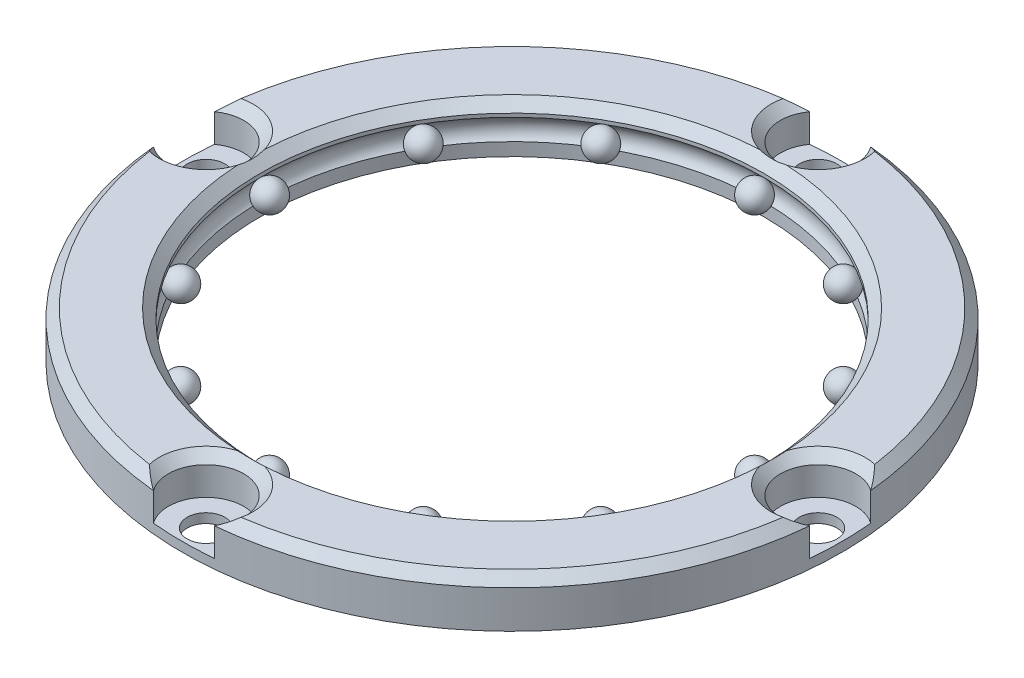
SolidWorks part; units mm, degrees
ref_plane "Front Plane" through (0, 0, 0) normal (0, 0, 1) x (1, 0, 0)
ref_plane "Top Plane" through (0, 0, 0) normal (0, 1, 0) x (1, 0, 0)
ref_plane "Right Plane" through (0, 0, 0) normal (1, 0, 0) x (0, 0, -1)
sketch "Sketch1" plane through (0, 0, 0) normal (0, 1, 0) x (1, 0, 0)
  line L0 (0, 0) -> (0, 19) construction
  circle A1 centre (0, 19) radius 8.5 construction
  circle A2 centre (19, 0) radius 3
  circle A3 centre (19, 0) radius 1.5313
  circle A5 centre (0, 19) radius 10 construction
  circle A10 centre (0, 19) radius 3
  circle A12 centre (0, -19) radius 3
  circle A14 centre (0, 19) radius 1.5313
  circle A17 centre (0, -19) radius 1.5313
  circle A18 centre (-19, 0) radius 3
  circle A19 centre (-19, 0) radius 1.5313
  point P13 (0, 0)
  point P24 (0, 0)
  point P26 (0, 0)
  point P30 (0, 0)
  dimension "D5" = 17
  dimension "D7" = 6
  dimension "D8" = 3.0625
  dimension "D2" = 19
  dimension "D3" = 19
  dimension "D6" = 19
sketch "Sketch2" plane through (0, 0, 0) normal (0, 1, 0) x (-1, 0, 0)
  line L0 (0, 0) -> (-13.435, 13.435) construction
  circle A0 centre (0, 0) radius 23.75
  circle A2 centre (0, 0) radius 19 construction
  circle A3 centre (-13.435, 13.435) radius 2.5
  circle A4 centre (13.435, 13.435) radius 2.5
  circle A8 centre (0, 0) radius 1.5875
  circle A9 centre (13.435, -13.435) radius 2.5
  circle A10 centre (0, 19) radius 2.5
  circle A11 centre (19, 0) radius 2.5
  circle A12 centre (0, -19) radius 2.5
  circle A13 centre (-19, 0) radius 2.5
  circle A14 centre (-13.435, -13.435) radius 2.5
  point P19 (0, 0)
  point P27 (0, 0)
  dimension "D1" = 3.175
  dimension "D2" = 47.5
  dimension "D4" = 5
  dimension "D6" = 5
  dimension "D3" = 4
  dimension "D5" = 4
extrude "Boss-Extrude2" add sketch "Sketch2" against normal blind 5 contours A0 A11 A10 A8 region at (23.0782, 0, 0)
sketch "Sketch3" plane through (0, 0, 0) normal (0, 1, 0) x (1, 0, 0)
  circle A0 centre (0, 19) radius 3.45
  circle A1 centre (19, 0) radius 3.45
  circle A2 centre (0, -19) radius 3.45
  circle A3 centre (-19, 0) radius 3.45
  point P12 (0, 0)
  dimension "D1" = 6.9
  dimension "D2" = 4
extrude "Cut-Extrude1" cut sketch "Sketch3" against normal blind 4
sketch "Sketch4" plane through (0, 0, 0) normal (0, 0, 1) x (1, 0, 0)
  line L0 (-23.75, -5) -> (-23.75, 0) construction
  line L1 (-23.75, 0) -> (-23.75, -5) construction
  line L2 (-23.75, 0) -> (-24.75, 0) construction
  line L3 (-27.75, 0) -> (-27.75, -5) construction
  line L4 (-27.75, -5) -> (-25.75, -5) construction
  line L5 (-23.75, -5) -> (-24.75, -5) construction
  line L6 (-25.75, -5) -> (-25.75, 0) construction
  line L7 (-25.75, -1.95) -> (-25.75, 0) construction
  line L8 (-24.75, 0) -> (-23.75, 0)
  line L11 (-23.75, -2.5) -> (-17.0406, -2.5) construction
  line L12 (-23.75, -5) -> (-24.75, -5) construction
  line L14 (-24.75, -5) -> (-23.75, -5)
  line L15 (-25.75, -3.05) -> (-25.75, -5) construction
  line L16 (-24.75, 0) -> (-24.75, -1.382)
  line L17 (-24.75, -5) -> (-24.75, -3.618)
  line L18 (-25.75, 0) -> (-27.75, 0) construction
  line L19 (-24.75, -5) -> (-23.75, -5) construction
  line L20 (-25.75, -5) -> (-27.75, -5) construction
  line L21 (-26.75, -5) -> (-26.75, -3.618)
  line L22 (-26.75, 0) -> (-26.75, -1.382)
  line L23 (-26.75, 0) -> (-35, 0)
  line L24 (-35, 0) -> (-35, -5)
  line L25 (-35, -5) -> (-26.75, -5)
  line L26 (23.75, -2.5) -> (-23.75, -2.5) construction
  line L27 (23.75, 0) -> (-23.75, 0) construction
  line L28 (23.75, -5) -> (23.75, 0) construction
  line L29 (0, -2.5) -> (0, 0) construction
  line L30 (-23.75, -2.5) -> (-35, -2.5) construction
  line L31 (-23.75, 0) -> (-23.75, -5)
  arc A5 (-26.75, -1.382) -> (-26.75, -3.618) centre (-25.75, -2.5) ccw
  arc A6 (-24.75, -3.618) -> (-24.75, -1.382) centre (-25.75, -2.5) ccw
  dimension "D1" = 1.5
  dimension "D3" = 1
  dimension "D2" = 2
  dimension "D4" = 35
revolve "Revolve1" add sketch "Sketch4" angle 360 about L29
sketch "Sketch5" plane through (0, 0, 0) normal (0, 1, 0) x (1, 0, 0)
  circle A0 centre (0, 0) radius 32.5 construction
  circle A1 centre (0, 32.5) radius 2
  circle A2 centre (32.5, 0) radius 2
  circle A3 centre (0, -32.5) radius 2
  circle A4 centre (-32.5, 0) radius 2
  point P14 (0, 0)
  dimension "D1" = 4
extrude "Cut-Extrude2" cut sketch "Sketch5" against normal blind 10
sketch "Sketch6" plane through (0, 0, 0) normal (0, 1, 0) x (1, 0, 0)
  circle A0 centre (0, -32.5) radius 4
  circle A1 centre (-32.5, 0) radius 4
  circle A2 centre (0, 32.5) radius 4
  circle A3 centre (32.5, 0) radius 4
  point P12 (0, 0)
  dimension "D1" = 8
extrude "Cut-Extrude3" cut sketch "Sketch6" against normal blind 4
chamfer "Chamfer2" distance 1 angle 45 9 edges at (0, 0, -26.75) (-28.5, 0, 0) (-24.7487, 0, -24.7487) (0, 0, -28.5) (24.7487, 0, -24.7487) (28.5, 0, 0) (24.7487, 0, 24.7487) (0, 0, 28.5) (-24.7487, 0, 24.7487)
sketch "Sketch7" plane through (0, 0, 0) normal (0, 1, 0) x (1, 0, 0)
  circle A0 centre (0, 0) radius 24.75
  circle A1 centre (13.435, 13.435) radius 2.5
  circle A2 centre (13.435, 13.435) radius 2.5
  circle A3 centre (-13.435, 13.435) radius 2.5
  circle A4 centre (-13.435, 13.435) radius 2.5
  circle A5 centre (0, 0) radius 1.5875
  circle A6 centre (0, 0) radius 1.5875
  circle A7 centre (-13.435, -13.435) radius 2.5
  circle A8 centre (-13.435, -13.435) radius 2.5
  circle A9 centre (13.435, -13.435) radius 2.5
  circle A10 centre (13.435, -13.435) radius 2.5
  circle A11 centre (-19, 0) radius 3.45
  circle A12 centre (-19, 0) radius 3.45
  circle A13 centre (0, -19) radius 3.45
  circle A14 centre (0, -19) radius 3.45
  circle A15 centre (19, 0) radius 3.45
  circle A16 centre (19, 0) radius 3.45
  circle A17 centre (0, 19) radius 3.45
  circle A18 centre (0, 19) radius 3.45
  dimension "D1" = 0
  dimension "D2" = 0
  dimension "D3" = 0
  dimension "D4" = 0
  dimension "D5" = 0
  dimension "D6" = 0
  dimension "D7" = 0
  dimension "D8" = 0
  dimension "D9" = 0
extrude "Boss-Extrude3" add sketch "Sketch7" along normal blind 0.25
chamfer "Chamfer3" distance 0.5 angle 45 10 edges at (0, 0.25, -15.55) (0, 0.25, 22.45) (13.435, 0.25, 15.935) (0, 0.25, 1.5875) (13.435, 0.25, -10.935) (0, 0.25, 24.75) (-13.435, 0.25, -10.935) (-13.435, 0.25, 15.935) (-19, 0.25, 3.45) (19, 0.25, 3.45)
sketch "Sketch8" plane through (0, 0, 0) normal (0, 0, 1) x (1, 0, 0)
  line L0 (25.75, -2.5) -> (0, -2.5) construction
  line L3 (-35, -5) -> (35, -5) construction
  line L4 (-26.75, -5) -> (26.75, -5) construction
  line L5 (26.75, -5) -> (24.75, -5) construction
  line L6 (-24.75, -5) -> (24.75, -5) construction
  line L10 (25.75, -1) -> (25.75, -4)
  arc A0 (25.75, -1) -> (25.75, -4) centre (25.75, -2.5) ccw
  point P0 (0, 0)
  dimension "D1" = 25.75
  dimension "D2" = 1.5
  dimension "D3" = 2.5
revolve "Revolve2" add sketch "Sketch8" angle 360 about L10
pattern_circular "CirPattern1" count 12 over 360 about axis through (0, -5, 0) along (0, 1, 0) of bodies 121
delete or keep bodies "Body-Delete/Keep 1" type delete bodies bodies 119
